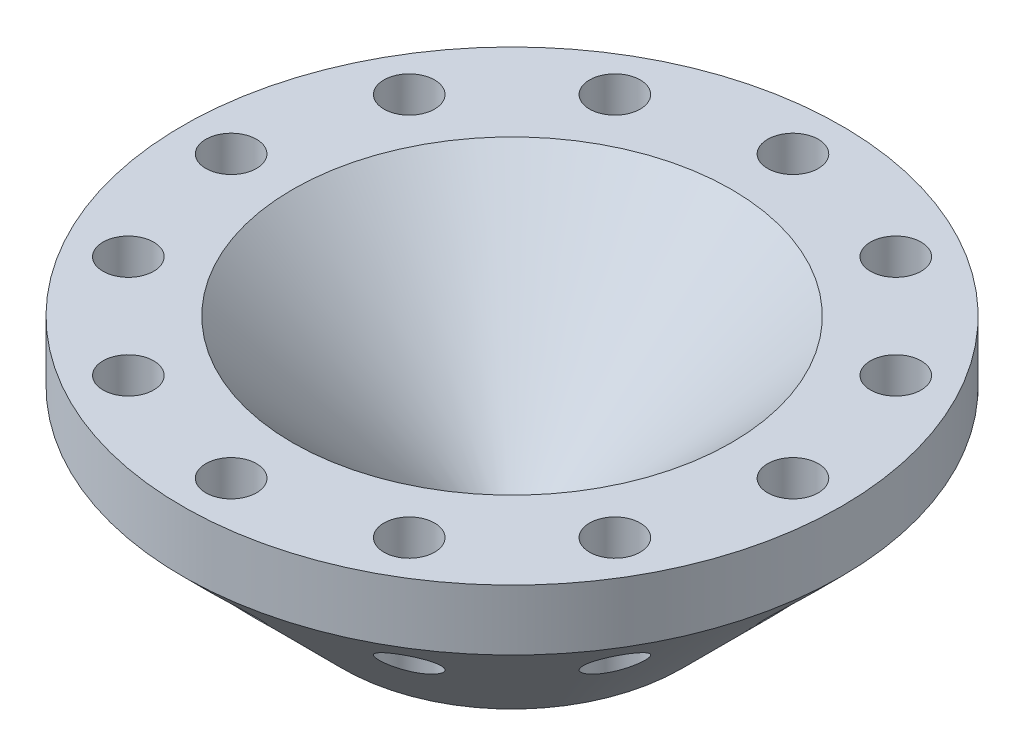
SolidWorks part; units mm, degrees
ref_plane "Front Plane" through (0, 0, 0) normal (0, 0, 1) x (1, 0, 0)
ref_plane "Top Plane" through (0, 0, 0) normal (0, 1, 0) x (1, 0, 0)
ref_plane "Right Plane" through (0, 0, 0) normal (1, 0, 0) x (0, 0, -1)
sketch "Sketch1" plane through (0, 0, 0) normal (0, 0, 1) x (1, 0, 0)
  line L17 (-19.9172, 20) -> (-29.9172, 20)
  line L18 (-29.9172, 20) -> (-29.9172, 14.5009)
  line L19 (-29.9172, 14.5009) -> (-15.4163, 0)
  line L21 (-15.4163, 0) -> (-26.2577, 0) construction
  line L22 (-19.9172, 20) -> (0, 0.0828)
  line L23 (-15.4163, 0) -> (0, 0)
  line L24 (0, 0) -> (0, 0.0828)
  point P4 (0, 2.3821)
  dimension "D3" = 20
  dimension "D1" = 10
  dimension "D2" = 45
  dimension "D4" = 5.4991
revolve "Revolve1" add sketch "Sketch1" angle 360 about L24
sketch "Sketch2" [suppressed] plane through (0, 0, 0) normal (0, -1, 0) x (1, 0, 0)
  circle A0 centre (0, 0) radius 12.7 construction
  circle A1 centre (0, 12.7) radius 2.032
  point P3 (0, 12.7)
  point P7 (8.9803, 8.9803)
  point P8 (12.7, 0)
  point P9 (8.9803, -8.9803)
  point P10 (0, -12.7)
  point P11 (-8.9803, -8.9803)
  point P12 (-12.7, 0)
  point P13 (-8.9803, 8.9803)
  point P14 (0, 0)
  dimension "D1" = 25.4
  dimension "D3" = 4.064
  dimension "D2" = 8
extrude "Cut-Extrude1" [suppressed] cut sketch "Sketch2" against normal up to next draft 4.35 contours A1
pattern_circular "CirPattern1" [suppressed] count 4 over 360 of bodies 102
sketch "Sketch5" plane through (0, 20, 0) normal (0, 1, 0) x (1, 0, 0)
  circle A0 centre (0, 0) radius 25.5 construction
  circle A1 centre (25.5, 0) radius 2.3
  dimension "D1" = 51
  dimension "D2" = 4.6
extrude "Cut-Extrude3" cut sketch "Sketch5" against normal up to next
pattern_circular "CirPattern2" count 12 over 360 about axis through (0, 20, 0) along (0, -1, 0) of "Cut-Extrude3"
